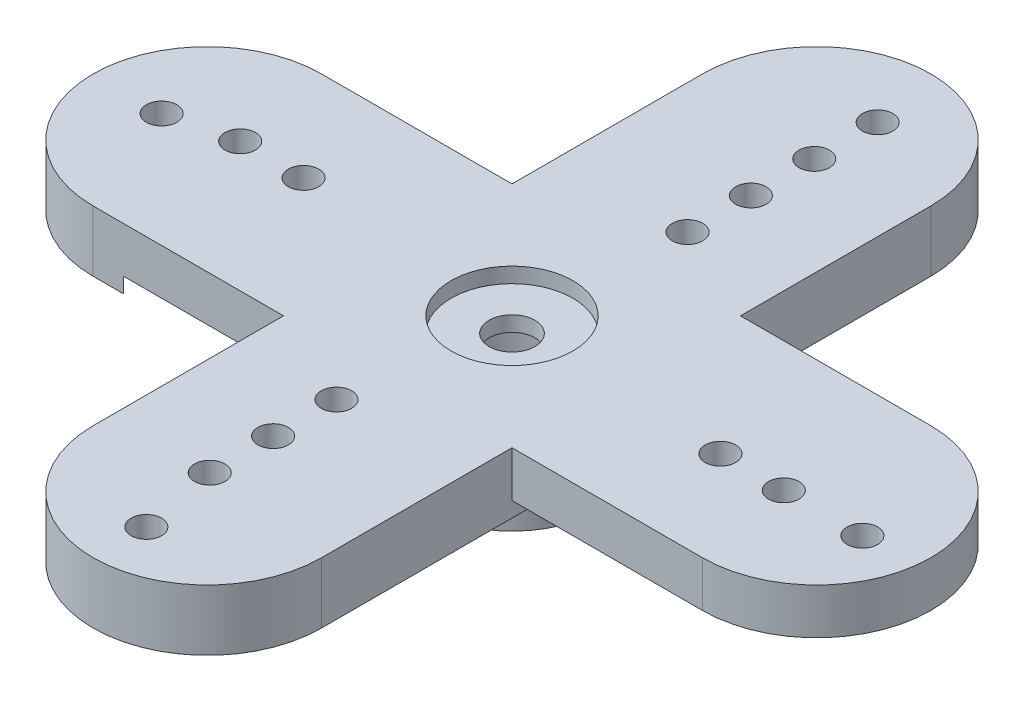
SolidWorks part; units mm, degrees
material "Custom Plastic"
ref_plane "Front Plane" through (0, 0, 0) normal (0, 0, 1) x (1, 0, 0)
ref_plane "Top Plane" through (0, 0, 0) normal (0, 1, 0) x (1, 0, 0)
ref_plane "Right Plane" through (0, 0, 0) normal (1, 0, 0) x (0, 0, -1)
sketch "Sketch1" plane through (0, 0, 0) normal (0, 1, 0) x (1, 0, 0)
  line L0 (5.9531, 15.875) -> (5.9531, 5.9521)
  line L1 (-5.9531, 15.875) -> (-5.9531, 5.9521)
  line L2 (0, -1000) -> (0, 49000) construction
  line L3 (-1000, 0) -> (49000, 0) construction
  line L4 (15.876, -5.9541) -> (5.9531, -5.9541)
  line L5 (15.876, 5.9521) -> (5.9531, 5.9521)
  line L6 (-5.9531, -5.9541) -> (-5.9531, -15.875)
  line L7 (5.9531, -5.9541) -> (5.9531, -15.875)
  line L8 (-5.9531, 5.9521) -> (-15.874, 5.9521)
  line L9 (-5.9531, -5.9541) -> (-15.874, -5.9541)
  arc A0 (-5.9531, 15.875) -> (5.9531, 15.875) centre (0, 15.875) cw
  arc A1 (-5.9531, -15.875) -> (5.9531, -15.875) centre (0, -15.875) ccw
  arc A2 (15.876, 5.9521) -> (15.876, -5.9541) centre (15.876, -0.001) cw
  arc A3 (-15.874, 5.9521) -> (-15.874, -5.9541) centre (-15.874, -0.001) ccw
  circle A4 centre (-18.2562, 0) radius 0.7937
  circle A5 centre (0.7938, 18.2562) radius 0.7937
  circle A6 centre (19.05, -0.7938) radius 0.7937
  circle A7 centre (0, -19.05) radius 0.7938
  circle A8 centre (0, 0) radius 1.1906
  circle A9 centre (0.7938, 14.9542) radius 0.7937
  circle A10 centre (0.7938, 11.6522) radius 0.7937
  circle A11 centre (14.9542, -0.7937) radius 0.7937
  circle A12 centre (11.6522, -0.7937) radius 0.7937
  circle A13 centre (-0.7937, -14.9542) radius 0.7937
  circle A14 centre (-0.7937, -11.6522) radius 0.7937
  circle A15 centre (-14.9542, 0.7937) radius 0.7937
  circle A16 centre (-11.6522, 0.7937) radius 0.7937
  circle A17 centre (0.7938, 8.3502) radius 0.7937
  circle A18 centre (-0.7937, -8.3502) radius 0.7937
  dimension "D3" = 5.9531
  dimension "D4" = 2
  dimension "D6" = 1.5875
  dimension "D9" = 2.3813
  dimension "D1" = 15.875
  dimension "D2" = 15.875
  dimension "D5" = 15.876
  dimension "D7" = 18.2562
  dimension "D14" = 19.05
  dimension "D10" = 3
  dimension "D12" = 2
  dimension "D13" = 2
  dimension "D8" = 4
  dimension "D11" = 4
extrude "Boss-Extrude1" add sketch "Sketch1" along normal blind 3.175
sketch "Sketch3" plane through (0, 0, 0) normal (0, -1, 0) x (1, 0, 0)
  line L0 (5.9531, -5.9521) -> (5.9531, 5.9541)
  line L1 (15.876, -5.9521) -> (5.9531, -5.9521)
  line L2 (15.876, 5.9541) -> (5.9531, 5.9541)
  line L4 (0.7938, -11.6522) -> (0.7938, 0.0102) construction
  line L5 (-14.2885, 5.9541) -> (-4.3656, 5.9541)
  line L6 (-14.2885, -5.9521) -> (-4.3656, -5.9521)
  line L7 (-4.3656, -5.9521) -> (-4.3656, 5.9541)
  arc A1 (15.876, -5.9521) -> (15.876, 5.9541) centre (15.876, 0.001) ccw
  arc A2 (-14.2885, -5.9521) -> (-14.2885, 5.9541) centre (-14.2885, 0.001) cw
extrude "Cut-Extrude1" cut sketch "Sketch3" against normal blind 0.7937
sketch "Sketch4" plane through (0, 3.175, 0) normal (0, 1, 0) x (1, 0, 0)
  circle A0 centre (0, 0) radius 3.175
extrude "Cut-Extrude2" cut sketch "Sketch4" against normal blind 0.7937
sketch "Sketch5" plane through (0, 0, 0) normal (0, -1, 0) x (1, 0, 0)
  circle A0 centre (0, 0) radius 4.7625
  circle A1 centre (0, 0) radius 3.048
extrude "Boss-Extrude2" add sketch "Sketch5" along normal blind 3.175 contours A1 | A0
sketch "Sketch6" plane through (0, 0, 0) normal (0, -1, 0) x (1, 0, 0)
  circle A0 centre (0, 0) radius 3.048
extrude "Cut-Extrude3" cut sketch "Sketch6" against normal blind 1.5875
